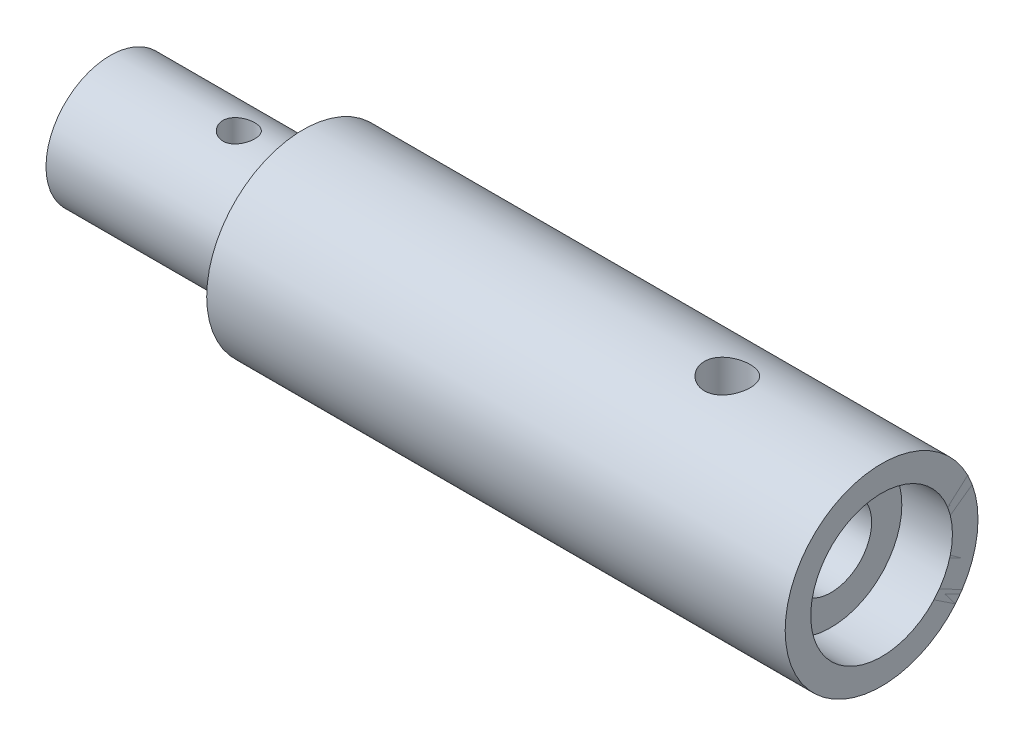
SolidWorks part; units mm, degrees
ref_plane "Front Plane" through (0, 0, 0) normal (0, 0, 1) x (1, 0, 0)
ref_plane "Top Plane" through (0, 0, 0) normal (0, 1, 0) x (1, 0, 0)
ref_plane "Right Plane" through (0, 0, 0) normal (1, 0, 0) x (0, 0, -1)
sketch "Sketch1" plane through (0, 0, 0) normal (1, 0, 0) x (0, 0, -1)
  circle A0 centre (0, 0) radius 4.7625
  dimension "D1" = 9.525
extrude "Boss-Extrude1" add sketch "Sketch1" along normal blind 38.1
sketch "Sketch2" plane through (38.1, 0, 0) normal (1, 0, 0) x (0, 0, -1)
  circle A0 centre (0, 0) radius 2.0066
extrude "Cut-Extrude1" cut sketch "Sketch2" against normal blind 10.414
sketch "Sketch3" plane through (0, 0, 0) normal (0, 1, 0) x (1, 0, 0)
  line L0 (38.1, -4.7625) -> (38.1, 4.7625) construction
  circle A0 centre (30.48, 0) radius 1.1303
  dimension "D1" = 7.62
extrude "Cut-Extrude2" cut sketch "Sketch3" along normal blind 8.6868
sketch "Sketch4" plane through (0, 0, 0) normal (-1, 0, 0) x (0, 0, 1)
  circle A0 centre (0, 0) radius 3.175
  circle A1 centre (0, 0) radius 5.0848
extrude "Cut-Extrude3" cut sketch "Sketch4" against normal blind 9.525
sketch "Sketch5" plane through (0, 0, 0) normal (0, 1, 0) x (1, 0, 0)
  line L0 (9.525, 4.7625) -> (9.525, -4.7625) construction
  circle A0 centre (6.35, 0) radius 0.7874
  dimension "D1" = 3.175
extrude "Cut-Extrude4" cut sketch "Sketch5" against normal through all and the other way through all
sketch "Sketch6" plane through (38.1, 0, 0) normal (1, 0, 0) x (0, 0, -1)
  circle A0 centre (0, 0) radius 3.5
  dimension "D1" = 7
extrude "Cut-Extrude5" cut sketch "Sketch6" against normal blind 2.5 contours A0
surface "Surface-Plane1"
ref_plane "Plane1" through (35.56, 0, 0) normal (1, 0, 0) x (0, 0, -1)
